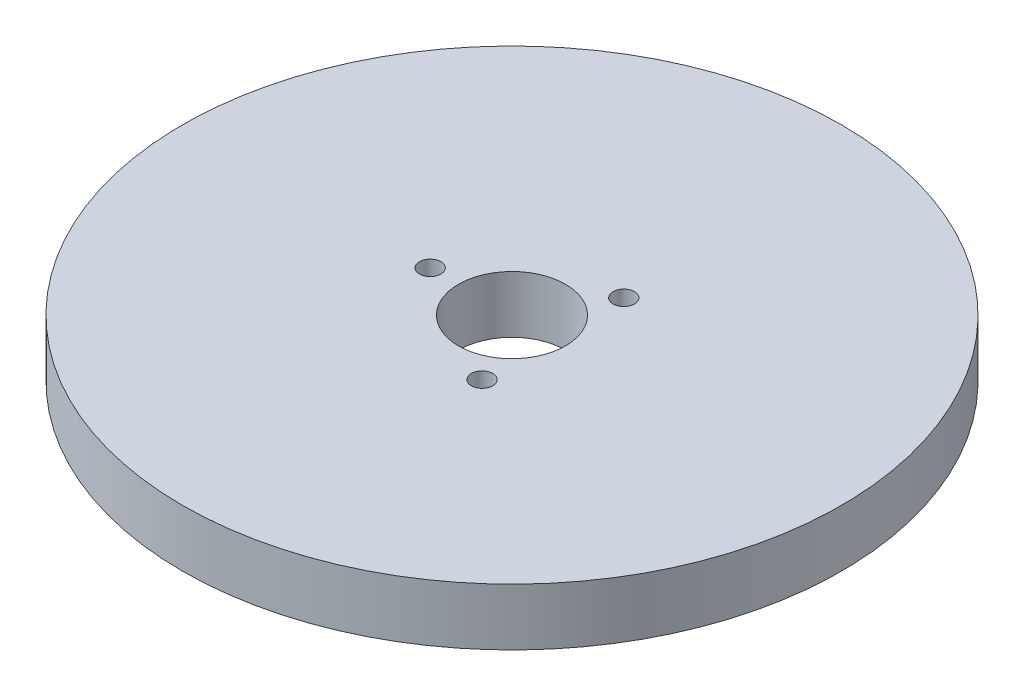
SolidWorks part; units mm, degrees
ref_plane "Front Plane" through (0, 0, 0) normal (0, 0, 1) x (1, 0, 0)
ref_plane "Top Plane" through (0, 0, 0) normal (0, 1, 0) x (1, 0, 0)
ref_plane "Right Plane" through (0, 0, 0) normal (1, 0, 0) x (0, 0, -1)
sketch "Sketch1" plane through (0, 0, 0) normal (0, 1, 0) x (1, 0, 0)
  circle A0 centre (0, 0) radius 92.5
  dimension "FLANGE_OD" = 185
extrude "Boss-Extrude1" add sketch "Sketch1" along normal blind 16
sketch "Sketch2" plane through (0, 0, 0) normal (0, 1, 0) x (1, 0, 0)
  circle A0 centre (0, 0) radius 15
  dimension "BORE_D" = 30
extrude "Cut-Extrude1" cut sketch "Sketch2" along normal through all
sketch "Sketch3" plane through (0, 16, 0) normal (0, 1, 0) x (1, 0, 0)
  circle A0 centre (0, 0) radius 22.9636 construction
  circle A1 centre (-22.9636, 0) radius 3.0059
  dimension "BOLT_D" = 6.0119
  dimension "BOLT_PCD" = 45.9272
extrude "Cut-Extrude2" cut sketch "Sketch3" against normal blind 10.4775
pattern_circular "CirPattern1" count 3 over 360 about axis through (0, 0, 0) along (0, 1, 0) of "Cut-Extrude2"
